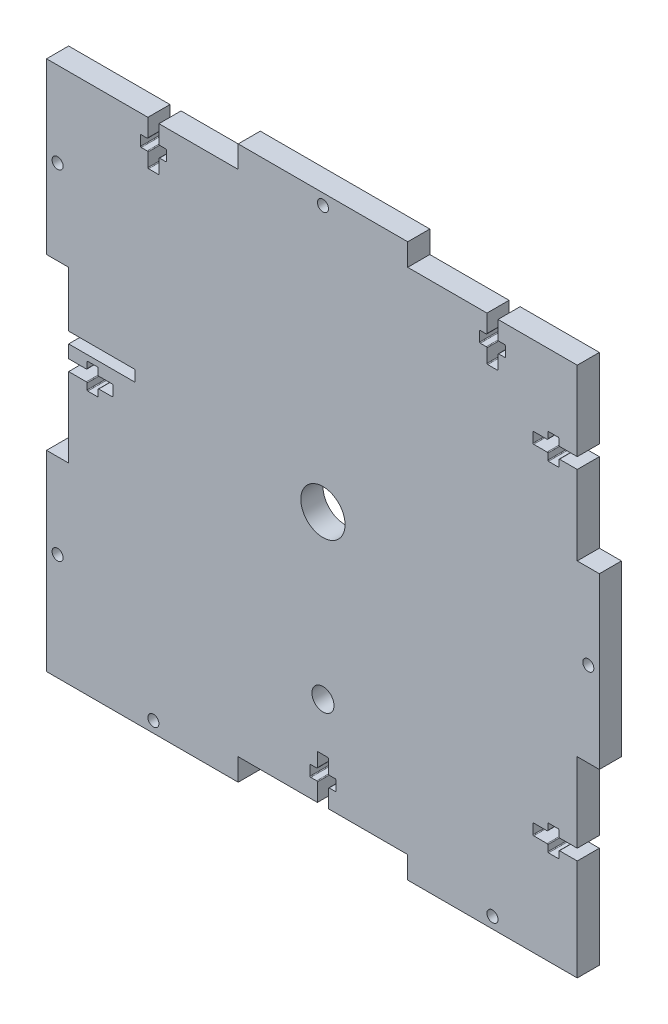
SolidWorks part; units mm, degrees
ref_plane "Front Plane" through (0, 0, 0) normal (0, 0, 1) x (1, 0, 0)
ref_plane "Top Plane" through (0, 0, 0) normal (0, 1, 0) x (1, 0, 0)
ref_plane "Right Plane" through (0, 0, 0) normal (1, 0, 0) x (0, 0, -1)
sketch "Sketch1" plane through (0, 0, 0) normal (0, 0, 1) x (1, 0, 0)
  line L0 (-69, 69) -> (-23, 69)
  line L5 (-75, -75) -> (75, -75) construction
  line L6 (-75, -75) -> (-75, 75) construction
  line L7 (-75, 75) -> (75, 75) construction
  line L8 (75, -75) -> (75, 75) construction
  line L9 (75, 23) -> (69, 23)
  line L10 (69, -23) -> (75, -23)
  line L11 (-69, -69) -> (69, -69) construction
  line L12 (-69, -69) -> (-69, 69) construction
  line L13 (-69, 69) -> (69, 69) construction
  line L14 (69, -69) -> (69, 69) construction
  line L15 (-69, -69) -> (69, 69) construction
  line L16 (69, -69) -> (69, -23)
  line L17 (-23, 69) -> (-23, 75)
  line L18 (-23, 75) -> (23, 75)
  line L19 (23, 75) -> (23, 69)
  line L20 (23, 69) -> (69, 69)
  line L21 (75, -23) -> (75, 23)
  line L22 (69, 23) -> (69, 69)
  line L23 (-75, 23) -> (-69, 23)
  line L24 (-69, 69) -> (-75, 69)
  line L25 (-75, 69) -> (-75, 23)
  line L26 (69, -69) -> (69, -75)
  line L27 (69, -75) -> (23, -75)
  line L28 (23, -75) -> (23, -69)
  line L29 (23, -69) -> (-23, -69)
  line L30 (-23, -69) -> (-23, -75)
  line L31 (-23, -75) -> (-69, -75)
  line L32 (-69, -75) -> (-69, -69) construction
  line L33 (-69, 23) -> (-69, -23)
  line L34 (-69, -23) -> (-75, -23)
  line L35 (-75, -23) -> (-75, -69)
  line L36 (-75, -69) -> (-69, -69) construction
  line L37 (-46, 69) -> (-46, -75) construction
  line L38 (-69, 69) -> (69, -69) construction
  line L39 (-75, -75) -> (-69, -75)
  line L40 (-75, -75) -> (-75, -69)
  point P0 (0, 0)
  point P6 (-7, -7)
  point P26 (0, -75)
  point P27 (-75, 0)
  dimension "D1" = 150
  dimension "D2" = 150
  dimension "D5" = 46
  dimension "D3" = 6
  dimension "D6" = 6
  dimension "D7" = 6
extrude "Box Side" add sketch "Sketch1" along normal blind 6
sketch "Sketch2" plane through (0, 0, 6) normal (0, 0, 1) x (1, 0, 0)
  line L0 (23, 72) -> (-23, 72) construction
  line L1 (23, 75) -> (23, 69) construction
  line L2 (-23, 69) -> (-23, 75) construction
  line L3 (-46, 69) -> (-46, -75) construction
  line L5 (0, 75) -> (0, 69) construction
  line L6 (-23, 75) -> (23, 75) construction
  line L7 (-69, 69) -> (69, 69) construction
  line L16 (-46, 69) -> (-46, -75) construction
  line L21 (0, -69) -> (0, 69) construction
  line L35 (-69, 69) -> (-23, 69) construction
  line L36 (-44.5, 69) -> (-44.5, 64.2)
  line L37 (-44.3, 64) -> (-42.7, 64)
  line L38 (-42.5, 63.8) -> (-42.5, 61.2)
  line L39 (-42.7, 61) -> (-44.3, 61)
  line L40 (-44.5, 60.8) -> (-44.5, 57.2)
  line L46 (-44.7, 57) -> (-47.3, 57)
  line L48 (-44.5, 69) -> (-47.5, 69)
  line L51 (-47.5, 60.8) -> (-47.5, 57.2)
  line L52 (-49.3, 61) -> (-47.7, 61)
  line L53 (-49.5, 63.8) -> (-49.5, 61.2)
  line L54 (-47.7, 64) -> (-49.3, 64)
  line L55 (-47.5, 69) -> (-47.5, 64.2)
  line L56 (47.5, 69) -> (47.5, 64.2)
  line L57 (47.7, 64) -> (49.3, 64)
  line L58 (49.5, 63.8) -> (49.5, 61.2)
  line L59 (49.3, 61) -> (47.7, 61)
  line L60 (47.5, 60.8) -> (47.5, 57.2)
  line L61 (44.5, 69) -> (47.5, 69)
  line L62 (44.7, 57) -> (47.3, 57)
  line L63 (44.5, 60.8) -> (44.5, 57.2)
  line L64 (42.7, 61) -> (44.3, 61)
  line L65 (42.5, 63.8) -> (42.5, 61.2)
  line L66 (44.3, 64) -> (42.7, 64)
  line L67 (44.5, 69) -> (44.5, 64.2)
  line L68 (-69, -69) -> (69, 69) construction
  line L69 (-69, -69) -> (69, 69) construction
  line L70 (75, 0) -> (69, 0) construction
  line L71 (72, 23) -> (72, -23) construction
  line L72 (69, 44.5) -> (64.2, 44.5)
  line L73 (64, 44.3) -> (64, 42.7)
  line L74 (63.8, 42.5) -> (61.2, 42.5)
  line L75 (61, 42.7) -> (61, 44.3)
  line L76 (60.8, 44.5) -> (57.2, 44.5)
  line L77 (57, 44.7) -> (57, 47.3)
  line L78 (69, 44.5) -> (69, 47.5)
  line L79 (60.8, 47.5) -> (57.2, 47.5)
  line L80 (61, 49.3) -> (61, 47.7)
  line L81 (63.8, 49.5) -> (61.2, 49.5)
  line L82 (64, 47.7) -> (64, 49.3)
  line L83 (69, 47.5) -> (64.2, 47.5)
  line L84 (69, -47.5) -> (64.2, -47.5)
  line L85 (64, -47.7) -> (64, -49.3)
  line L86 (63.8, -49.5) -> (61.2, -49.5)
  line L87 (61, -49.3) -> (61, -47.7)
  line L88 (60.8, -47.5) -> (57.2, -47.5)
  line L89 (69, -44.5) -> (69, -47.5)
  line L90 (57, -44.7) -> (57, -47.3)
  line L91 (60.8, -44.5) -> (57.2, -44.5)
  line L92 (61, -42.7) -> (61, -44.3)
  line L93 (63.8, -42.5) -> (61.2, -42.5)
  line L94 (64, -44.3) -> (64, -42.7)
  line L95 (69, -44.5) -> (64.2, -44.5)
  line L120 (-69, 69) -> (69, -69) construction
  line L121 (-69, 69) -> (69, -69) construction
  line L122 (-1.5, -69) -> (1.5, -69)
  line L123 (-23, -69) -> (23, -69) construction
  line L124 (1.5, -69) -> (1.5, -64.2)
  line L125 (1.7, -64) -> (3.3, -64)
  line L126 (3.5, -63.8) -> (3.5, -61.2)
  line L127 (3.3, -61) -> (1.7, -61)
  line L128 (1.5, -60.8) -> (1.5, -57.2)
  line L129 (1.3, -57) -> (-1.3, -57)
  line L130 (-1.5, -60.8) -> (-1.5, -57.2)
  line L131 (-3.3, -61) -> (-1.7, -61)
  line L132 (-3.5, -63.8) -> (-3.5, -61.2)
  line L133 (-1.7, -64) -> (-3.3, -64)
  line L134 (-1.5, -69) -> (-1.5, -64.2)
  line L135 (-69, -1.5) -> (-64.2, -1.5)
  line L136 (-64, -1.7) -> (-64, -3.3)
  line L137 (-63.8, -3.5) -> (-61.2, -3.5)
  line L138 (-61, -3.3) -> (-61, -1.7)
  line L139 (-60.8, -1.5) -> (-57.2, -1.5)
  line L140 (-57, 1.3) -> (-57, -1.3)
  line L141 (-60.8, 1.5) -> (-57.2, 1.5)
  line L142 (-61, 3.3) -> (-61, 1.7)
  line L143 (-63.8, 3.5) -> (-61.2, 3.5)
  line L144 (-64, 1.7) -> (-64, 3.3)
  line L145 (-69, 1.5) -> (-64.2, 1.5)
  line L146 (-69, -1.5) -> (-69, 1.5)
  line L147 (-69, -72) -> (-23, -72) construction
  line L148 (-23, 69) -> (-75, 69) construction
  line L149 (-23, -75) -> (-23, -69) construction
  line L150 (-69, -69) -> (-69, -75) construction
  line L151 (-75, -75) -> (-23, -75) construction
  circle A0 centre (0, 72) radius 1.5
  arc A1 (-44.5, 57.2) -> (-44.7, 57) centre (-44.7, 57.2) cw
  arc A2 (-44.3, 61) -> (-44.5, 60.8) centre (-44.3, 60.8) ccw
  arc A3 (-42.5, 61.2) -> (-42.7, 61) centre (-42.7, 61.2) cw
  arc A4 (-42.7, 64) -> (-42.5, 63.8) centre (-42.7, 63.8) cw
  arc A5 (-44.5, 64.2) -> (-44.3, 64) centre (-44.3, 64.2) ccw
  arc A6 (-47.5, 64.2) -> (-47.7, 64) centre (-47.7, 64.2) cw
  arc A7 (-49.3, 64) -> (-49.5, 63.8) centre (-49.3, 63.8) ccw
  arc A8 (-49.5, 61.2) -> (-49.3, 61) centre (-49.3, 61.2) ccw
  arc A9 (-47.7, 61) -> (-47.5, 60.8) centre (-47.7, 60.8) cw
  arc A10 (-47.5, 57.2) -> (-47.3, 57) centre (-47.3, 57.2) ccw
  arc A11 (47.5, 57.2) -> (47.3, 57) centre (47.3, 57.2) cw
  arc A12 (47.7, 61) -> (47.5, 60.8) centre (47.7, 60.8) ccw
  arc A13 (49.5, 61.2) -> (49.3, 61) centre (49.3, 61.2) cw
  arc A14 (49.3, 64) -> (49.5, 63.8) centre (49.3, 63.8) cw
  arc A15 (47.5, 64.2) -> (47.7, 64) centre (47.7, 64.2) ccw
  arc A16 (44.5, 64.2) -> (44.3, 64) centre (44.3, 64.2) cw
  arc A17 (42.7, 64) -> (42.5, 63.8) centre (42.7, 63.8) ccw
  arc A18 (42.5, 61.2) -> (42.7, 61) centre (42.7, 61.2) ccw
  arc A19 (44.3, 61) -> (44.5, 60.8) centre (44.3, 60.8) cw
  arc A20 (44.5, 57.2) -> (44.7, 57) centre (44.7, 57.2) ccw
  arc A21 (57.2, 44.5) -> (57, 44.7) centre (57.2, 44.7) cw
  arc A22 (61, 44.3) -> (60.8, 44.5) centre (60.8, 44.3) ccw
  arc A23 (61.2, 42.5) -> (61, 42.7) centre (61.2, 42.7) cw
  arc A24 (64, 42.7) -> (63.8, 42.5) centre (63.8, 42.7) cw
  arc A25 (64.2, 44.5) -> (64, 44.3) centre (64.2, 44.3) ccw
  arc A26 (64.2, 47.5) -> (64, 47.7) centre (64.2, 47.7) cw
  arc A27 (64, 49.3) -> (63.8, 49.5) centre (63.8, 49.3) ccw
  arc A28 (61.2, 49.5) -> (61, 49.3) centre (61.2, 49.3) ccw
  arc A29 (61, 47.7) -> (60.8, 47.5) centre (60.8, 47.7) cw
  arc A30 (57.2, 47.5) -> (57, 47.3) centre (57.2, 47.3) ccw
  arc A31 (57.2, -47.5) -> (57, -47.3) centre (57.2, -47.3) cw
  arc A32 (61, -47.7) -> (60.8, -47.5) centre (60.8, -47.7) ccw
  arc A33 (61.2, -49.5) -> (61, -49.3) centre (61.2, -49.3) cw
  arc A34 (64, -49.3) -> (63.8, -49.5) centre (63.8, -49.3) cw
  arc A35 (64.2, -47.5) -> (64, -47.7) centre (64.2, -47.7) ccw
  arc A36 (64.2, -44.5) -> (64, -44.3) centre (64.2, -44.3) cw
  arc A37 (64, -42.7) -> (63.8, -42.5) centre (63.8, -42.7) ccw
  arc A38 (61.2, -42.5) -> (61, -42.7) centre (61.2, -42.7) ccw
  arc A39 (61, -44.3) -> (60.8, -44.5) centre (60.8, -44.3) cw
  arc A40 (57.2, -44.5) -> (57, -44.7) centre (57.2, -44.7) ccw
  circle A41 centre (72, 0) radius 1.5
  arc A62 (1.5, -57.2) -> (1.3, -57) centre (1.3, -57.2) ccw
  arc A63 (1.7, -61) -> (1.5, -60.8) centre (1.7, -60.8) cw
  arc A64 (3.5, -61.2) -> (3.3, -61) centre (3.3, -61.2) ccw
  arc A65 (3.3, -64) -> (3.5, -63.8) centre (3.3, -63.8) ccw
  arc A66 (1.5, -64.2) -> (1.7, -64) centre (1.7, -64.2) cw
  arc A67 (-1.5, -64.2) -> (-1.7, -64) centre (-1.7, -64.2) ccw
  arc A68 (-3.3, -64) -> (-3.5, -63.8) centre (-3.3, -63.8) cw
  arc A69 (-3.5, -61.2) -> (-3.3, -61) centre (-3.3, -61.2) cw
  arc A70 (-1.7, -61) -> (-1.5, -60.8) centre (-1.7, -60.8) ccw
  arc A71 (-1.5, -57.2) -> (-1.3, -57) centre (-1.3, -57.2) cw
  arc A72 (-57.2, -1.5) -> (-57, -1.3) centre (-57.2, -1.3) ccw
  arc A73 (-61, -1.7) -> (-60.8, -1.5) centre (-60.8, -1.7) cw
  arc A74 (-61.2, -3.5) -> (-61, -3.3) centre (-61.2, -3.3) ccw
  arc A75 (-64, -3.3) -> (-63.8, -3.5) centre (-63.8, -3.3) ccw
  arc A76 (-64.2, -1.5) -> (-64, -1.7) centre (-64.2, -1.7) cw
  arc A77 (-64.2, 1.5) -> (-64, 1.7) centre (-64.2, 1.7) ccw
  arc A78 (-64, 3.3) -> (-63.8, 3.5) centre (-63.8, 3.3) cw
  arc A79 (-61.2, 3.5) -> (-61, 3.3) centre (-61.2, 3.3) cw
  arc A80 (-61, 1.7) -> (-60.8, 1.5) centre (-60.8, 1.7) ccw
  arc A81 (-57.2, 1.5) -> (-57, 1.3) centre (-57.2, 1.3) cw
  circle A82 centre (-46, -72) radius 1.5
  circle A83 centre (46, -72) radius 1.5
  circle A84 centre (-72, 46) radius 1.5
  circle A85 centre (-72, -46) radius 1.5
  point P6 (0, 72)
  point P38 (0, 0)
  point P56 (-46, 57)
  point P88 (46, 57)
  point P161 (57, 46)
  point P162 (57, -46)
  point P198 (0, -57)
  point P231 (-57, 0)
  point P234 (-42.5, 62.5)
  dimension "D1" = 3
  dimension "D2" = 0.2
  dimension "D8" = 0.2
  dimension "D14" = 3
  dimension "D4" = 3
  dimension "D7" = 1.5
  dimension "D10" = 3
  dimension "D12" = 1.5
  dimension "D9" = 12
  dimension "D11" = 5
  dimension "D13" = 7
  dimension "D3" = 12
  dimension "D5" = 7
  dimension "D6" = 5
extrude "Screw Cut-outs" cut sketch "Sketch2" against normal through all
sketch "Sketch3" plane through (0, 0, 6) normal (0, 0, 1) x (1, 0, 0)
  line L0 (-69, -69) -> (69, 69) construction
  line L1 (-69, -69) -> (69, 69) construction
  line L2 (-69, 69) -> (69, -69) construction
  line L3 (-69, 69) -> (69, -69) construction
  circle A0 centre (0, 0) radius 6
  point P4 (0, 0)
  dimension "D1" = 12
extrude "BearingHole" cut sketch "Sketch3" against normal through all
sketch "Sketch4" plane through (0, 0, 6) normal (0, 0, 1) x (1, 0, 0)
  line L0 (-69, 23) -> (-69, 1.5) construction
  line L1 (-69, 5) -> (-51, 5)
  line L2 (-69, 5) -> (-69, 8)
  line L3 (-69, 8) -> (-51, 8)
  line L4 (-51, 5) -> (-51, 8)
  line L5 (-61.2, 3.5) -> (-63.8, 3.5) construction
  dimension "D1" = 3
  dimension "D2" = 1.5
  dimension "D3" = 18
extrude "Cut-Extrude1" cut sketch "Sketch4" against normal up to surface (6 mm away) up to face at (6, 0, 0)
sketch "Sketch5" plane through (0, 0, 6) normal (0, 0, 1) x (1, 0, 0)
  line L0 (1.5, -69) -> (23, -69) construction
  circle A0 centre (0, -44) radius 3
  dimension "D1" = 6
  dimension "D2" = 25
extrude "Cut-Extrude2" cut sketch "Sketch5" against normal through all
equation "\"filletRadius\"=0.2"
equation "\"D8@Sketch2\"=\"filletRadius\""
equation "\"D2@Sketch2\"=\"filletRadius\""
equation "\"fingerWidth\"= 46"
equation "\"D5@Sketch1\"=\"fingerWidth\""
equation "\"wallThickness\"= 6"
equation "\"D3@Sketch1\" = \"wallThickness\""
equation "\"D6@Sketch1\" = \"wallThickness\""
equation "\"D7@Sketch1\" = \"wallThickness\""
equation "\"D1@Box Side\" = \"wallThickness\""
equation "\"M3\"= 3"
equation "\"D14@Sketch2\"=\"M3\""
equation "\"D1@Sketch2\"=\"M3\""
equation "\"D12@Sketch2\"=\"M3\"/2"
equation "\"nutThickness\"=3"
equation "\"D10@Sketch2\" = \"nutThickness\""
equation "\"boltLength\"= 12"
equation "\"D9@Sketch2\" = \"boltLength\""
equation "\"distanceToNut\"= 5"
equation "\"D11@Sketch2\" = \"distanceToNut\""
equation "\"D13@Sketch2\" = \"nutWidth\""
equation "\"D7@Sketch2\"=\"M3\"/2"
equation "\"D4@Sketch2\" = \"nutThickness\""
equation "\"D3@Sketch2\" = \"boltLength\""
equation "\"D5@Sketch2\" = \"nutWidth\""
equation "\"D6@Sketch2\" = \"distanceToNut\""
equation "\"sideLength\"=150"
equation "\"D1@Sketch1\"=\"sideLength\""
equation "\"D2@Sketch1\"=\"sideLength\""
equation "\"nutWidth\"=7"
